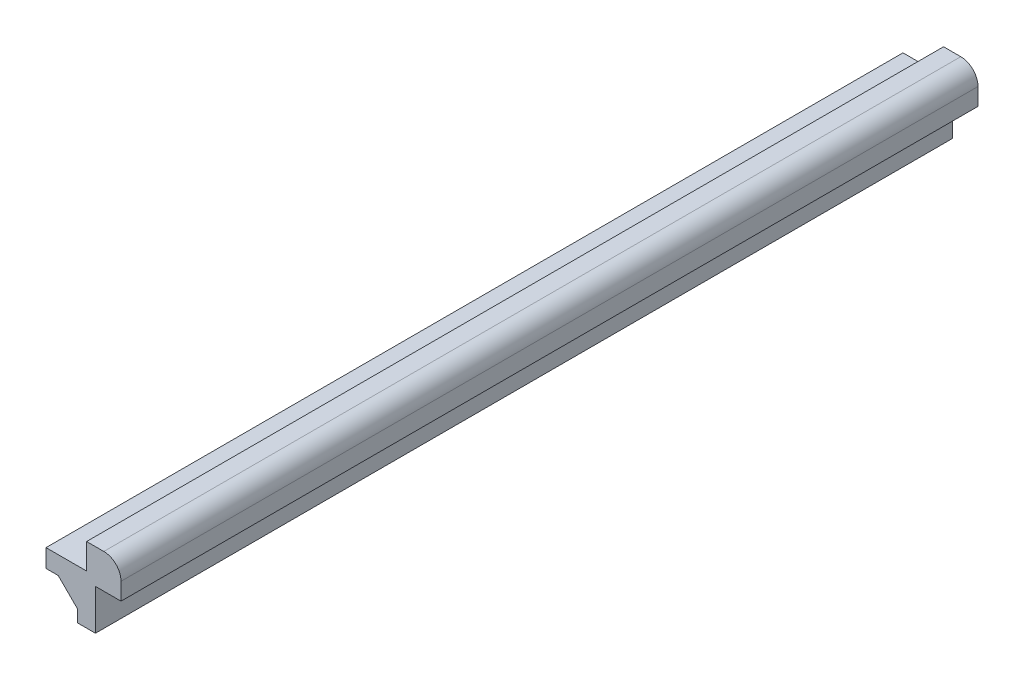
SolidWorks part; units mm, degrees
ref_plane "Front Plane" through (0, 0, 0) normal (0, 0, 1) x (1, 0, 0)
ref_plane "Top Plane" through (0, 0, 0) normal (0, 1, 0) x (1, 0, 0)
ref_plane "Right Plane" through (0, 0, 0) normal (1, 0, 0) x (0, 0, -1)
ref_axis "Axis1" through (0, 0, -88.99) along (0, 0, 1)
sketch "Sketch16" plane through (0, 0, 0) normal (0, 1, 0) x (1, 0, 0)
  line L0 (0, -47.0979) -> (0, 47.0979) construction
  point P2 (0, 0)
  dimension "D1" = 94.1959
sketch "Sketch2" plane through (0, 0, 0) normal (0, 0, 1) x (1, 0, 0)
  line L0 (-7.3025, -1.5) -> (-2.54, -1.5) construction
  line L1 (-7.3025, -1.5) -> (-7.3025, 1.5) construction
  line L2 (-2.54, -1.5) -> (-2.54, 1.5) construction
  line L3 (-7.3025, 1.5) -> (-2.54, 1.5) construction
  line L4 (-2.54, 0) -> (0, 0) construction
  line L5 (0, 0) -> (0, -2.54) construction
  line L6 (-1.5, -2.54) -> (1.5, -2.54) construction
  line L7 (-1.5, -2.54) -> (-1.5, -7.3025) construction
  line L8 (1.5, -2.54) -> (1.5, -7.3025) construction
  line L9 (-1.5, -7.3025) -> (1.5, -7.3025) construction
  point P7 (0, -2.54)
  point P16 (1.5, 1.5)
  dimension "D1" = 3
  dimension "D2" = 4.7625
  dimension "D3" = 2.54
  dimension "D4" = 90
ref_plane "Plane1" through (0, 0, 0) normal (-1, 0, 0) x (0, -1, 0)
sketch "Sketch7" plane through (0, 0, 0) normal (0, 0, 1) x (1, 0, 0)
  line L0 (-7.3025, -1.5) -> (-2.54, -1.5)
  line L1 (-7.3025, -1.5) -> (-7.3025, -3.6212)
  line L2 (-2.54, -1.5) -> (-2.54, -3.6212)
  line L3 (-7.3025, -3.6212) -> (-2.54, -3.6212)
  dimension "D1" = 2.1212
extrude "Boss-Extrude2" add sketch "Sketch7" along normal mid plane 100.5459 separate body
sketch "Sketch8" plane through (0, 0, 0) normal (0, 0, 1) x (1, 0, 0)
  line L0 (-1.5, -2.54) -> (-1.5, -7.3025)
  line L1 (-1.5, -2.54) -> (-3.6212, -2.54)
  line L2 (-1.5, -7.3025) -> (-3.6212, -7.3025)
  line L3 (-3.6212, -2.54) -> (-3.6212, -7.3025)
  line L4 (-2.54, -3.6212) -> (-2.54, -1.5) construction
extrude "Boss-Extrude3" add sketch "Sketch8" along normal mid plane 100.5459
sketch "Sketch11" plane through (0, 0, 0) normal (0, 0, 1) x (1, 0, 0)
  line L0 (-2.54, 1.5) -> (-2.54, -1.5)
  line L1 (-2.54, -1.5) -> (-7.3025, -1.5)
  line L2 (-7.3025, -1.5) -> (-7.3025, -3.6212)
  line L3 (-7.3025, -3.6212) -> (-5.8663, -3.6212)
  line L4 (-7.3025, -3.6212) -> (-3.6212, -3.6212) construction
  line L5 (-5.8663, -3.6212) -> (-3.6212, -5.8663)
  line L6 (-3.6212, -3.6212) -> (-3.6212, -7.3025) construction
  line L7 (-3.6212, -5.8663) -> (-3.6212, -7.3025)
  line L8 (-3.6212, -7.3025) -> (-1.5, -7.3025)
  line L9 (-1.5, -7.3025) -> (-1.5, -2.54)
  line L10 (-1.5, -2.54) -> (1.5, -2.54)
  line L13 (-2.54, 1.5) -> (-2.54, -2.54) construction
  line L14 (-2.54, -2.54) -> (1.5, -2.54) construction
  line L15 (1.5, -0.52) -> (1.5, -2.54)
  line L17 (-2.54, 1.5) -> (-0.52, 1.5)
  circle A0 centre (-0.52, -0.52) radius 2.02 construction
  arc A1 (-0.52, 1.5) -> (1.5, -0.52) centre (-0.52, -0.52) cw
  dimension "D1" = 3.175
extrude "Boss-Extrude4" add sketch "Sketch11" along normal mid plane 100.5459
ref_plane "Midplane" through (0, 0, 0) normal (-0.7071, 0.7071, 0) x (0.7071, 0.7071, 0)
equation "\"plate_thickness\"= 3mm"
equation "\"D1@Sketch2\"=\"plate_thickness\""
equation "\"joiner_lip_width\"= .1875"
equation "\"D2@Sketch2\"=\"joiner_lip_width\""
equation "\"face_gap\"=0.1"
equation "\"D3@Sketch2\"=\"face_gap\""
equation "\"inside_angle\"= 90"
equation "\"joiner_thickness\"= 0.0835128"
equation "\"edge_length\"= 3.7085"
equation "\"Face1_TopLip\"= \"angle\" * 2"
equation "\"Face1_BottomLip\"= \"angle\" * 2"
equation "\"Face2_TopLip\"= 45deg"
equation "\"Face2_BottomLip\"= 45deg"
equation "\"D1@Sketch7\"=\"joiner_thickness\""
equation "\"D1@Boss-Extrude2\"=\"Extrude_to\""
equation "\"D1@Boss-Extrude3\"=\"Extrude_to\""
equation "\"D1@Boss-Extrude4\"=\"Extrude_to\""
equation "\"D4@Sketch2\"=\"inside_angle\""
equation "\"Extrude_to\"= \"edge_length\" + .25"
equation "\"D1@Sketch16\"=\"edge_length\""
equation "\"angle\"= atn ( 0.1 / ( ( 3.7085 - 3.0793 ) / 2 ) )"
equation "\"D2@Sketch5\"=\"Face2_TopLip\"/2"
equation "\"D1@Sketch5\"=\"Face2_BottomLip\"/2"
equation "\"D2@Sketch4\"=\"Face1_TopLip\"/2"
equation "\"D1@Sketch4\"=\"Face1_BottomLip\"/2"
equation "\"D1\" = \"edge_length\""
equation "\"D2@Sketch12\"=\"Face1_TopLip\"/2"
equation "\"D1@Sketch12\"=\"Face1_BottomLip\"/2"
